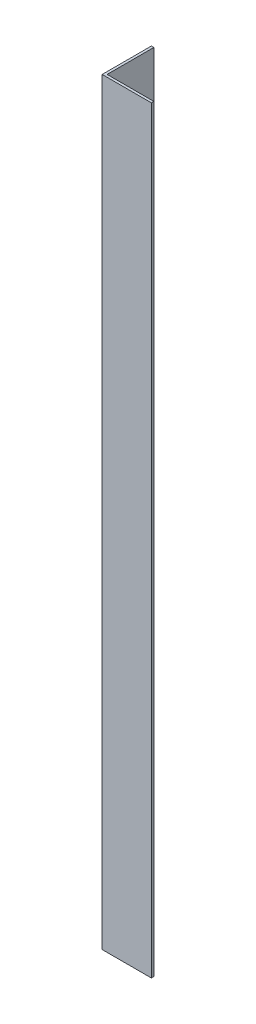
SolidWorks part; units mm, degrees
material "1060 Сплав"
ref_plane "Спереди" through (0, 0, 0) normal (0, 0, 1) x (1, 0, 0)
ref_plane "Сверху" through (0, 0, 0) normal (0, 1, 0) x (1, 0, 0)
ref_plane "Справа" through (0, 0, 0) normal (1, 0, 0) x (0, 0, -1)
sketch "Эскиз1" plane through (0, 0, 0) normal (0, 1, 0) x (1, 0, 0)
  line L0 (0, 0) -> (0, 15)
  line L1 (0, 15) -> (0.75, 15)
  line L2 (0.75, 15) -> (0.75, 0.75)
  line L3 (0.75, 0.75) -> (15, 0.75)
  line L4 (15, 0.75) -> (15, 0)
  line L5 (15, 0) -> (0, 0)
  dimension "D1" = 0.75
  dimension "D2" = 15
extrude "Бобышка-Вытянуть1" add sketch "Эскиз1" along normal blind 231
